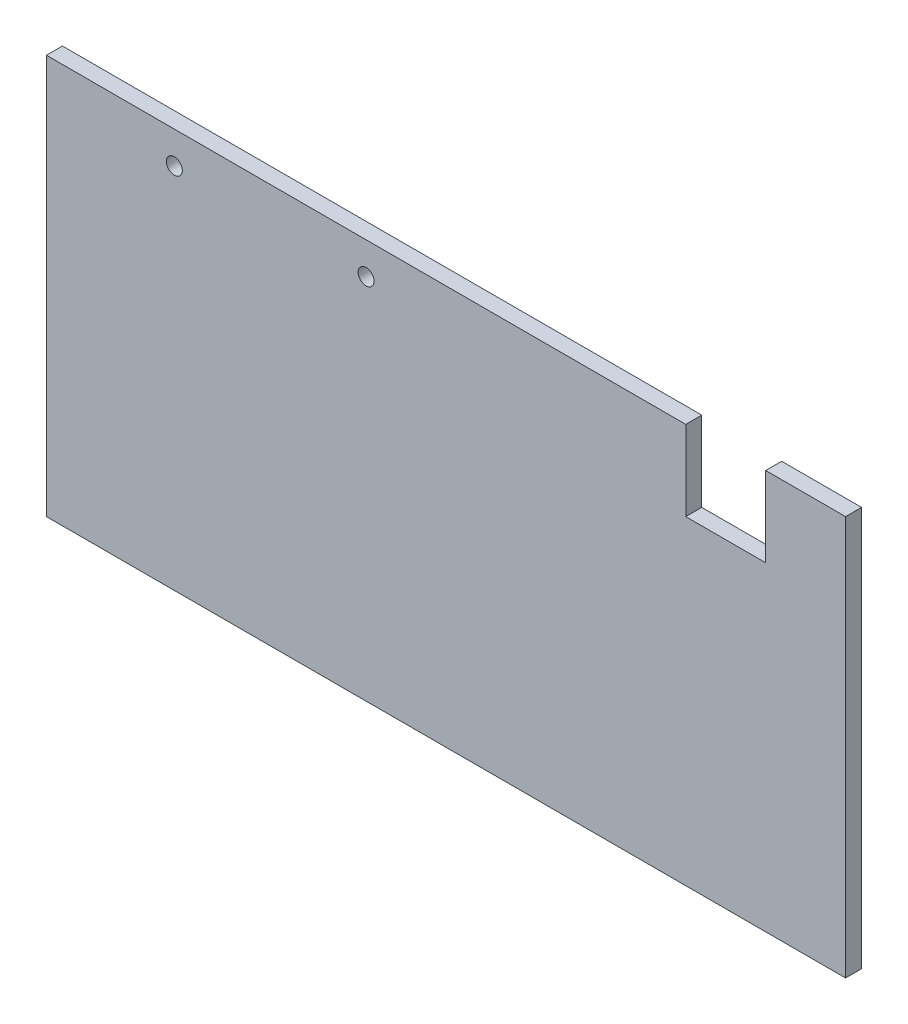
SolidWorks part; units mm, degrees
ref_plane "Front Plane" through (0, 0, 0) normal (0, 0, 1) x (1, 0, 0)
ref_plane "Top Plane" through (0, 0, 0) normal (0, 1, 0) x (1, 0, 0)
ref_plane "Right Plane" through (0, 0, 0) normal (1, 0, 0) x (0, 0, -1)
sketch "Sketch1" plane through (0, 0, 0) normal (0, 0, 1) x (1, 0, 0)
  line L0 (150, 125) -> (150, 75)
  line L1 (250, -125) -> (-250, -125)
  line L2 (250, -125) -> (250, 125)
  line L3 (250, 125) -> (200, 125)
  line L4 (-250, -125) -> (-250, 125)
  line L5 (250, -125) -> (-250, 125) construction
  line L6 (250, 125) -> (-250, -125) construction
  line L7 (150, 75) -> (200, 75)
  line L8 (200, 75) -> (200, 125)
  line L9 (150, 125) -> (-250, 125)
  point P0 (0, 0)
  dimension "D1" = 500
  dimension "D2" = 250
  dimension "D3" = 50
  dimension "D4" = 50
  dimension "D5" = 50
extrude "Boss-Extrude1" add sketch "Sketch1" along normal blind 10
sketch "Sketch3" plane through (0, 0, 10) normal (0, 0, 1) x (1, 0, 0)
  line L0 (-250, 125) -> (-250, -125) construction
  line L1 (150, 125) -> (-250, 125) construction
  circle A0 centre (-50, 105) radius 5
  circle A1 centre (-170, 105) radius 5
  dimension "D1" = 120
  dimension "D2" = 10
  dimension "D4" = 200
  dimension "D3" = 20
extrude "Cut-Extrude1" cut sketch "Sketch3" against normal up to next
